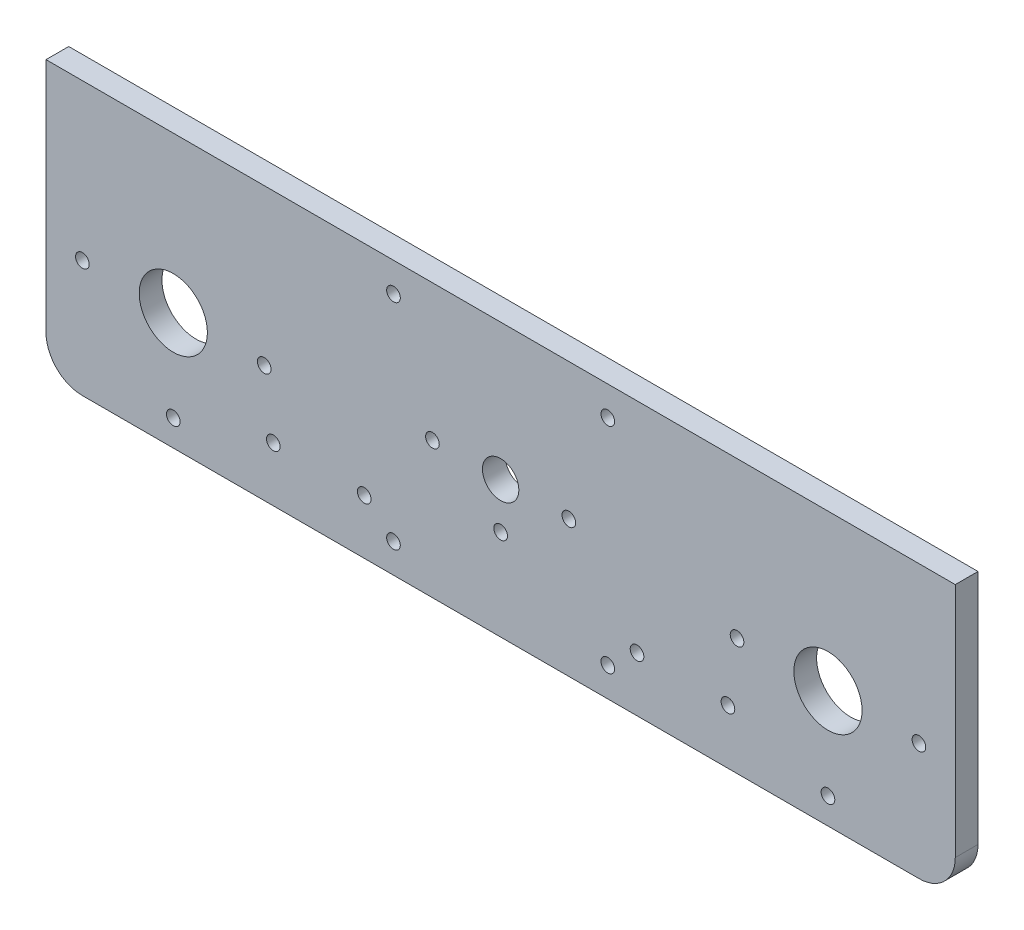
SolidWorks part; units mm, degrees
ref_plane "Alzado" through (0, 0, 0) normal (0, 0, 1) x (1, 0, 0)
ref_plane "Planta" through (0, 0, 0) normal (0, 1, 0) x (1, 0, 0)
ref_plane "Vista lateral" through (0, 0, 0) normal (1, 0, 0) x (0, 0, -1)
sketch "Croquis1" plane through (0, 0, 0) normal (0, 0, 1) x (1, 0, 0)
  line L0 (2.0685, -12.3273) -> (102.0685, -12.3273) construction
  line L1 (2.0685, -12.3273) -> (2.0685, -27.3273) construction
  line L2 (74.0685, -12.3273) -> (74.0685, -31.5773) construction
  line L3 (102.0685, -12.3273) -> (102.0685, -49.3273)
  line L4 (94.0685, -57.3273) -> (-89.9315, -57.3273)
  line L5 (2.0685, -57.3273) -> (2.0685, -27.3273) construction
  line L6 (2.0685, -12.3273) -> (2.0685, 2.6727) construction
  line L7 (-97.9315, 2.6727) -> (102.0685, 2.6727)
  line L8 (102.0685, 2.6727) -> (102.0685, -12.3273)
  line L9 (-97.9315, 2.6727) -> (-97.9315, -12.3273)
  line L10 (-97.9315, -12.3273) -> (-97.9315, -49.3273)
  line L11 (2.0685, -27.3273) -> (102.0685, -27.3273) construction
  line L12 (-21.5015, -50.8973) -> (25.6385, -50.8973) construction
  line L13 (-21.5015, -50.8973) -> (-21.5015, -3.7573) construction
  line L14 (-21.5015, -3.7573) -> (25.6385, -3.7573) construction
  line L15 (25.6385, -50.8973) -> (25.6385, -3.7573) construction
  line L16 (-21.5015, -50.8973) -> (25.6385, -3.7573) construction
  line L17 (-21.5015, -3.7573) -> (25.6385, -50.8973) construction
  circle A0 centre (2.0685, -27.3273) radius 4
  circle A1 centre (74.0685, -31.5773) radius 7.5
  circle A2 centre (-69.9315, -31.5773) radius 7.5
  circle A3 centre (74.0685, -51.5773) radius 1.5
  circle A4 centre (54.0685, -31.5773) radius 1.5
  circle A5 centre (94.0685, -31.5773) radius 1.5
  circle A6 centre (-69.9315, -31.5773) radius 7.5
  circle A7 centre (-69.9315, -51.5773) radius 1.5
  circle A8 centre (-89.9315, -31.5773) radius 1.5
  circle A9 centre (-49.9315, -31.5773) radius 1.5
  arc A10 (102.0685, -49.3273) -> (94.0685, -57.3273) centre (94.0685, -49.3273) cw
  arc A11 (-97.9315, -49.3273) -> (-89.9315, -57.3273) centre (-89.9315, -49.3273) ccw
  circle A12 centre (32.0685, -45.3273) radius 1.5
  circle A13 centre (52.0685, -45.3273) radius 1.5
  circle A14 centre (-47.9315, -45.3273) radius 1.5
  circle A15 centre (-27.9315, -45.3273) radius 1.5
  circle A16 centre (-12.9315, -27.3273) radius 1.5
  circle A17 centre (17.0685, -27.3273) radius 1.5
  circle A18 centre (2.0685, -37.3273) radius 1.5
  circle A19 centre (-21.5015, -3.7573) radius 1.5
  circle A20 centre (25.6385, -3.7573) radius 1.5
  circle A21 centre (25.6385, -50.8973) radius 1.5
  circle A22 centre (-21.5015, -50.8973) radius 1.5
  dimension "D4" = 8
  dimension "D5" = 15
  dimension "D10" = 3
  dimension "D11" = 3
  dimension "D13" = 8
  dimension "D14" = 3
  dimension "D15" = 3
  dimension "D19" = 3
  dimension "D21" = 3
  dimension "D24" = 3
  dimension "D1" = 19.25
  dimension "D2" = 15
  dimension "D3" = 72
  dimension "D6" = 100
  dimension "D7" = 47.14
  dimension "D8" = 20
  dimension "D9" = 20
  dimension "D12" = 15
  dimension "D16" = 20
  dimension "D17" = 30
  dimension "D18" = 12
  dimension "D20" = 15
  dimension "D22" = 10
  dimension "D23" = 47.14
extrude "Saliente-Extruir1" add sketch "Croquis1" along normal blind 5 contours L10 A11 L4 A10 L3 L8 L7 L9 A20 A19 A18 A15 A7 A2 A1 A0 A3 A4 A5 A8 A9 A12 A13 A14 A16 A17 A21 A22 region at (99.9804, -30.8273, 0)
